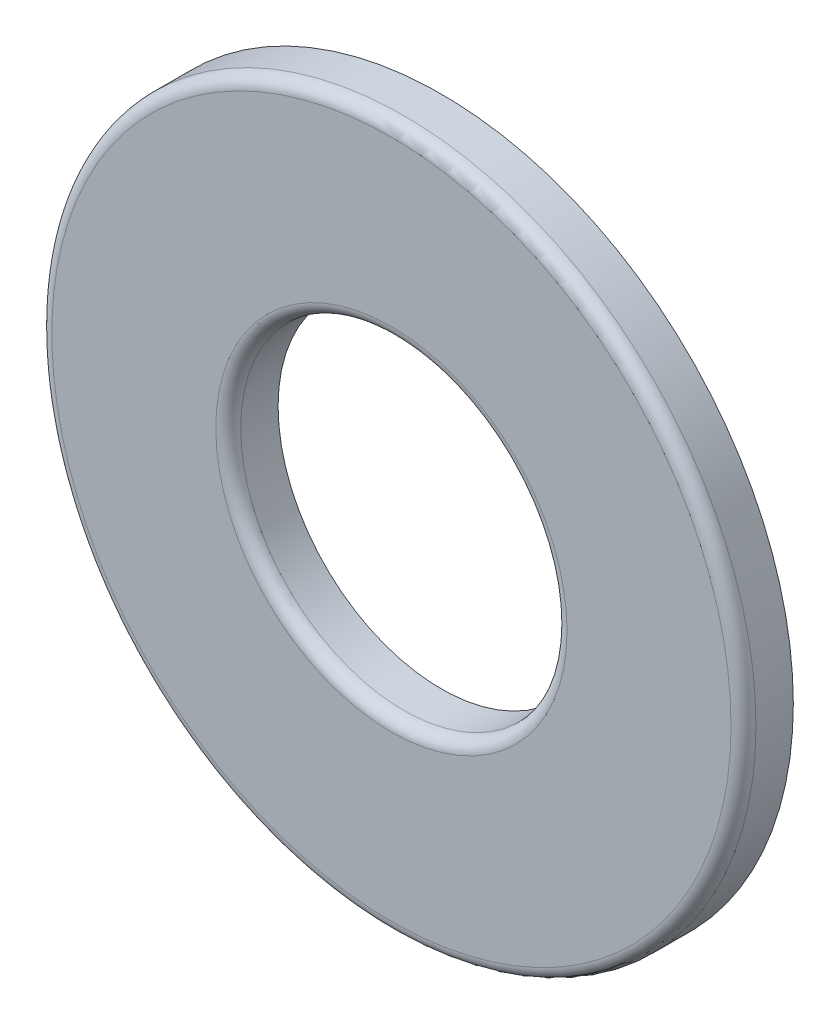
SolidWorks part; units mm, degrees
note: '?' marks a value the reader was unsure of.
other "Imported1" parameters "D1"=0.1968, "TH"=1.0287, "Thickness"=0.7874
ref_plane "Front Plane" through (0, 0, 0) normal (0, 0, 1) x (1, 0, 0)
ref_plane "Top Plane" through (0, 0, 0) normal (0, 1, 0) x (1, 0, 0)
ref_plane "Right Plane" through (0, 0, 0) normal (1, 0, 0) x (0, 0, -1)
sketch "Sketch1" plane through (0, 0, 0) normal (0, 0, 1) x (1, 0, 0)
  line L0 (-5.5626, 0) -> (5.5626, 0) construction
  line L1 (-2.5781, 0) -> (2.5781, 0) construction
  circle A0 centre (0, 0) radius 2.5781 construction
  circle A1 centre (0, 0) radius 5.5626 construction
  point P8 (0, 0)
  point P9 (0, 5.5626)
  point P11 (2.5781, 0)
  dimension "ID" = 5.1562
  dimension "OD" = 11.1252
sketch "Sketch2" plane through (0, 0, 0) normal (1, 0, 0) x (0, 0, -1)
  line L0 (-0.3937, 5.5626) -> (0.3937, 5.5626) construction
  point P2 (0, 5.5626)
sketch "Sketch3" plane through (0, 0, 0) normal (0, 0, 1) x (1, 0, 0)
  circle A0 centre (0, 0) radius 2.5781
  circle A1 centre (0, 0) radius 5.5626
extrude "Boss-Extrude1" add sketch "Sketch3" along normal up to vertex (0.3937 mm away) and the other way up to vertex (0.3937 mm away) up to point (0, 5.5626, 0.3937) other way up to point (0, 5.5626, -0.3937)
fillet "Fillet1" radius 0.1968 2 edges at (5.5626, 0, 0.3937) (2.5781, 0, 0.3937)
ref_axis "Center Axis 1" through (0, 0, 0.1968) along (0, 0, -1)?
equation "\"D1@Fillet1\"=\"Thickness@Sketch2\"/4"
